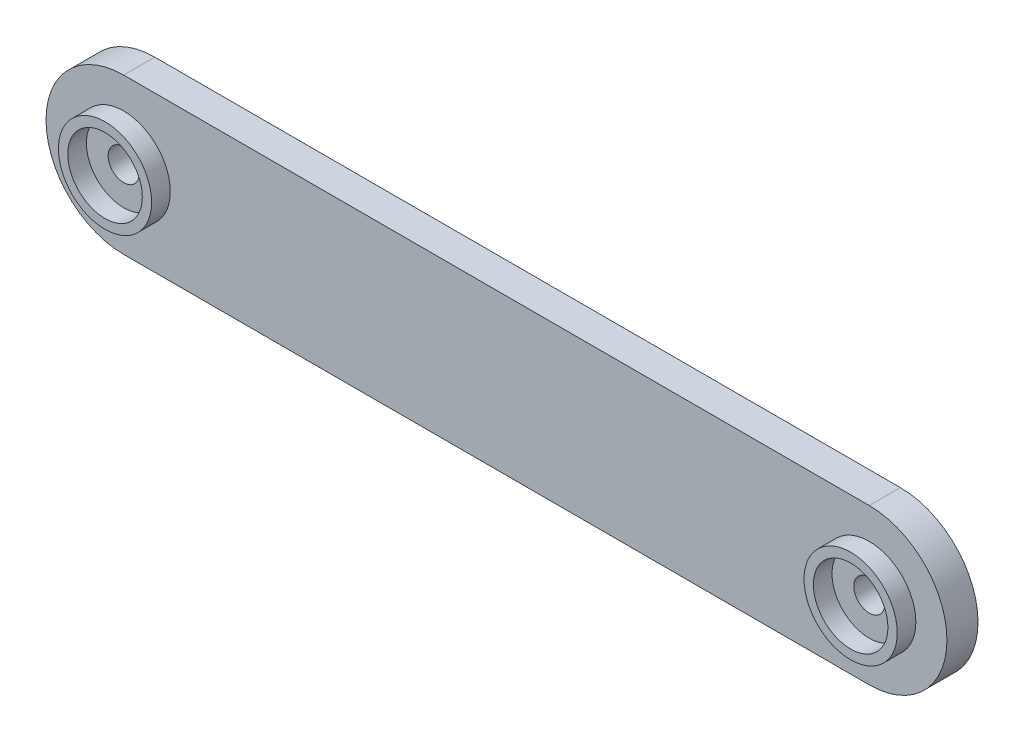
SolidWorks part; units mm, degrees
ref_plane "Front Plane" through (0, 0, 0) normal (0, 0, 1) x (1, 0, 0)
ref_plane "Top Plane" through (0, 0, 0) normal (0, 1, 0) x (1, 0, 0)
ref_plane "Right Plane" through (0, 0, 0) normal (1, 0, 0) x (0, 0, -1)
sketch "Sketch1" plane through (0, 0, 0) normal (0, 0, 1) x (1, 0, 0)
  line L1 (0, 0) -> (120, 0)
  line L2 (0, 0) -> (0, 25)
  line L3 (0, 25) -> (120, 25)
  line L4 (120, 0) -> (120, 25)
  line L5 (120, 15) -> (120, 10)
  circle A0 centre (0, 12.5) radius 12.5
  circle A4 centre (120, 12.5) radius 12.5
  dimension "D1" = 25
  dimension "D4" = 120
extrude "Boss-Extrude2" add sketch "Sketch1" along normal blind 5 contours L2 L1 L4 L3 | A0 | A4
sketch "Sketch3" plane through (0, 0, 5) normal (0, 0, 1) x (1, 0, 0)
  line L0 (0, 0) -> (120, 0) construction
  line L1 (0, 25) -> (120, 25) construction
  line L2 (0, 0) -> (120, 0) construction
  line L3 (0, 25) -> (120, 25) construction
  arc A0 (120, 0) -> (120, 25) centre (120, 12.5) ccw construction
  arc A1 (0, 25) -> (0, 0) centre (0, 12.5) ccw construction
  arc A2 (120, 0) -> (120, 25) centre (120, 12.5) ccw construction
  arc A3 (0, 25) -> (0, 0) centre (0, 12.5) ccw construction
  circle A4 centre (0, 12.5) radius 2.5
  circle A5 centre (120, 12.5) radius 2.5
  circle A6 centre (0, 12.5) radius 6
  circle A7 centre (0, 12.5) radius 7.5
  circle A8 centre (120, 12.5) radius 6
  circle A9 centre (120, 12.5) radius 7.5
  dimension "D1" = 5
  dimension "D2" = 5
  dimension "D3" = 12
  dimension "D4" = 15
  dimension "D5" = 12
  dimension "D6" = 15
extrude "Cut-Extrude3" cut sketch "Sketch3" against normal up to next contours A4 | A5
extrude "Boss-Extrude3" add sketch "Sketch3<3>" along normal blind 3 contours A7 A6 | A9 A8 region at (-7.2879, 12.5, 5) region at (112.7121, 12.5, 5)
sketch "Sketch3<3>" plane through (0, 0, 5) normal (0, 0, 1) x (1, 0, 0) same geometry as "Sketch3"
equation "\"LinkMiddle_Length\"=120"
equation "\"D4@Sketch1\"=\"LinkMiddle_Length\""
